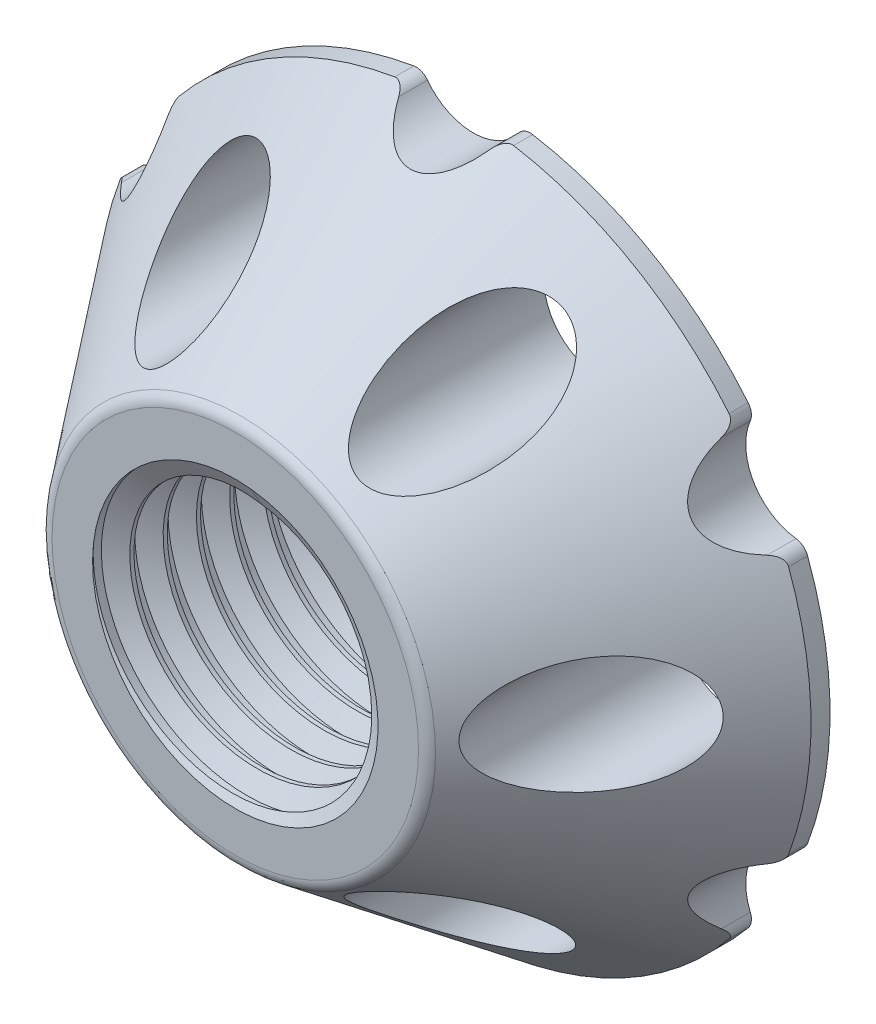
SolidWorks part; units mm, degrees
ref_plane "Front Plane" through (0, 0, 0) normal (0, 0, 1) x (1, 0, 0)
ref_plane "Top Plane" through (0, 0, 0) normal (0, 1, 0) x (1, 0, 0)
ref_plane "Right Plane" through (0, 0, 0) normal (1, 0, 0) x (0, 0, -1)
sketch "Sketch2" plane through (0, 0, 0) normal (1, 0, 0) x (0, 0, -1)
  line L0 (-25, 0) -> (0, 0)
  line L1 (0, 0) -> (0, 37.5)
  line L2 (0, 37.5) -> (-2, 37.5)
  line L3 (-2, 37.5) -> (-25, 20)
  line L4 (-25, 20) -> (-25, 0)
  dimension "D1" = 37.5
  dimension "D2" = 20
  dimension "D3" = 25
  dimension "D4" = 2
revolve "Revolve1" add sketch "Sketch2" angle 360 about L0
sketch "Sketch4" plane through (0, 0, 25) normal (0, 0, 1) x (1, 0, 0)
  circle A0 centre (0, 0) radius 15
  dimension "D1" = 30
extrude "Cut-Extrude1" cut sketch "Sketch4" against normal through all
ref_plane "Plane1" through (0, 0, -7) normal (0, 0, 1) x (1, 0, 0)
sketch "Sketch3" plane through (0, 0, -7) normal (0, 0, 1) x (1, 0, 0)
  circle A0 centre (0, 0) radius 13.8635
  dimension "D1" = 27.727
curve "Helix/Spiral1" pitch 3.5 height 38.5 radius 13.8635 left hand yes centre (0, 0, -7) axis (0, 0, 1) start towards (1, 0, 0)
sketch "Sketch5" plane through (0, 0, 0) normal (0, 1, 0) x (1, 0, 0)
  line L0 (0, 0) -> (0, 7) construction
  line L1 (0, 7) -> (13.1055, 7) construction
  line L2 (0, 7) -> (0, 9) construction
  line L3 (0, 9) -> (15, 9) construction
  line L4 (15, 9) -> (15, 5) construction
  line L5 (13.1055, 7.2188) -> (13.1055, 6.7812) construction
  line L6 (13.1055, 7) -> (17.1055, 7) construction
  line L7 (13.1055, 7.2188) -> (16.5696, 9.2188) construction
  line L8 (13.1055, 6.7812) -> (16.5696, 4.7812) construction
  line L9 (13.1055, 7.2188) -> (15, 8.3125)
  line L10 (15, 8.3125) -> (15, 5.6875)
  line L11 (15, 5.6875) -> (13.1055, 6.7812)
  line L12 (13.1055, 6.7812) -> (13.1055, 7.2188)
  point P9 (15, 8.3125)
  point P13 (15, 5.6875)
  dimension "D1" = 7
  dimension "D2" = 13.1055
  dimension "D3" = 2
  dimension "D4" = 15
  dimension "D5" = 4
  dimension "D6" = 0.2188
  dimension "D7" = 0.4375
  dimension "D8" = 4
  dimension "D9" = 4
  dimension "D10" = 4
  dimension "D11" = 60
  dimension "D12" = 30
sweep "Sweep1" add profiles "Sketch5" path "Helix/Spiral1"
sketch "Sketch7" plane through (0, 0, 0) normal (0, 1, 0) x (1, 0, 0)
  line L0 (37.5, 0) -> (-37.5, 0) construction
  line L1 (20, 0) -> (-20, 0)
  line L2 (20, 0) -> (20, 10)
  line L3 (20, 10) -> (-20, 10)
  line L4 (-20, 0) -> (-20, 10)
  line L5 (-20, -25) -> (20, -25) construction
  line L6 (-20, -25) -> (20, -25)
  line L7 (-20, -25) -> (-20, -35)
  line L8 (-20, -35) -> (20, -35)
  line L9 (20, -25) -> (20, -35)
  dimension "D1" = 40
  dimension "D2" = 10
  dimension "D3" = 20
  dimension "D4" = 40
  dimension "D5" = 10
  dimension "D6" = 20
extrude "Cut-Extrude2" cut sketch "Sketch7" against normal through all both and the other way through all
sketch "Sketch8" plane through (0, 0, 0) normal (0, 1, 0) x (1, 0, 0)
  line L0 (15, 0) -> (0, 0) construction
  line L1 (37.5, 0) -> (-37.5, 0) construction
  line L2 (0, 0) -> (0, -25) construction
  line L3 (-20, -25) -> (20, -25) construction
  line L4 (0, -25) -> (15, -25) construction
  line L5 (15, 0) -> (11.5, 0)
  line L6 (11.5, 0) -> (11.5, -2.0207)
  line L7 (11.5, -2.0207) -> (15, 0)
  line L8 (15, -25) -> (11.5, -25)
  line L9 (11.5, -25) -> (11.5, -22.9793)
  line L10 (11.5, -22.9793) -> (15, -25)
  dimension "D1" = 15
  dimension "D2" = 15
  dimension "D3" = 30
  dimension "D4" = 3.5
  dimension "D5" = 30
  dimension "D6" = 3.5
revolve "Cut-Revolve2" cut sketch "Sketch8" angle 360 about L2
sketch "Sketch9" plane through (0, 0, 0) normal (0, 0, -1) x (-1, 0, 0)
  line L0 (0, 0) -> (0, 40) construction
  line L1 (0, 0) -> (34.641, 20) construction
  circle A0 centre (0, 40) radius 6
  circle A1 centre (34.641, 20) radius 6
  circle A2 centre (34.641, -20) radius 6
  circle A3 centre (0, -40) radius 6
  circle A4 centre (-34.641, -20) radius 6
  circle A5 centre (-34.641, 20) radius 6
  point P17 (0, 0)
  dimension "D1" = 40
  dimension "D2" = 12
  dimension "D5" = 34.641
  dimension "D4" = 60
  dimension "D3" = 6
extrude "Cut-Extrude3" cut sketch "Sketch9" against normal through all
sketch "Sketch10" plane through (0, 0, 0) normal (0, 0, -1) x (-1, 0, 0)
  line L0 (0, 0) -> (0, 27.5) construction
  line L1 (0, 0) -> (13.75, 23.8157) construction
  line L2 (0, 0) -> (26.875, 0) construction
  circle A0 centre (0, 0) radius 27.5
  circle A1 centre (13.75, 23.8157) radius 6
  circle A2 centre (26.875, 0) radius 6
  circle A3 centre (12.8125, -23.2744) radius 6
  circle A4 centre (-14.375, -22.7332) radius 6
  circle A5 centre (-27.5, 1.0825) radius 6
  circle A6 centre (-13.4375, 24.357) radius 6
  point P18 (-0.3125, 0.5413)
  dimension "D1" = 55
  dimension "D3" = 12
  dimension "D5" = 13.125
  dimension "D2" = 30
  dimension "D4" = 6
extrude "Cut-Extrude4" cut sketch "Sketch10" against normal through all contours A6 | A1 | A2 | A3 | A4 | A5
fillet "Fillet1" radius 1.5 13 edges at (-34.7879, -14.0018, 1) (-29.5199, -23.1263, 1) (-5.268, -37.1281, 1) (5.268, -37.1281, 1) (29.5199, -23.1263, 1) (34.7879, -14.0018, 1) (34.7879, 14.0018, 1) (29.5199, 23.1263, 1) (5.268, 37.1281, 1) (-5.268, 37.1281, 1) (-34.7879, 14.0018, 1) (-29.5199, 23.1263, 1) (20, 0, 25)
sketch "Sketch11" plane through (0, 0, 0) normal (1, 0, 0) x (0, 0, -1)
  line L0 (10, 0) -> (-40, 0) construction
  dimension "D1" = 50
  dimension "D2" = 10
